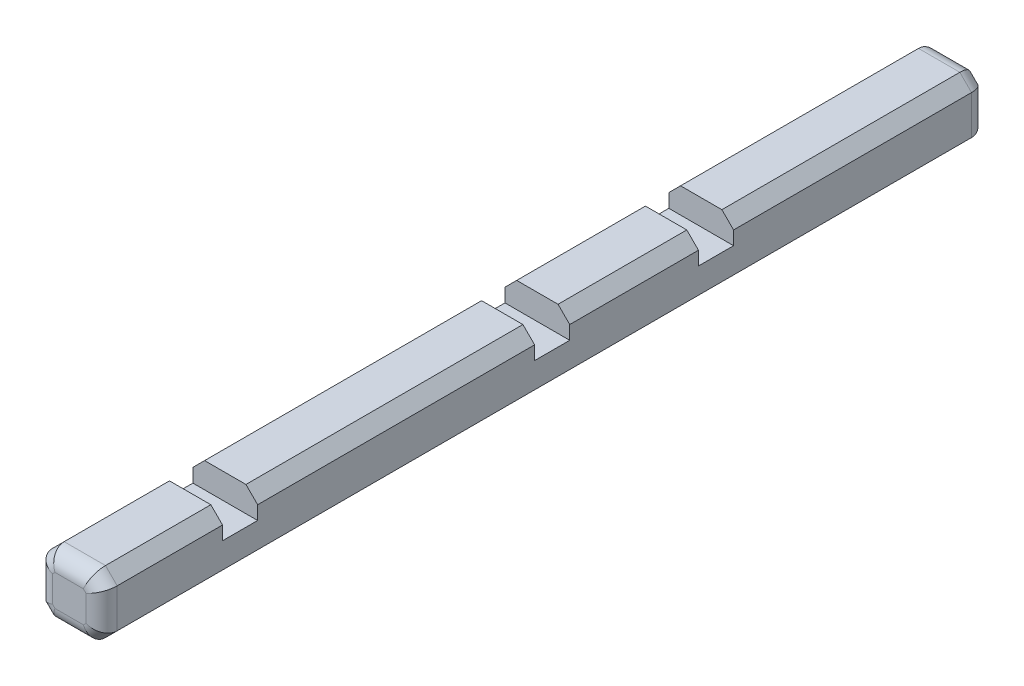
SolidWorks part; units mm, degrees
ref_plane "Front Plane" through (0, 0, 0) normal (0, 0, 1) x (1, 0, 0)
ref_plane "Top Plane" through (0, 0, 0) normal (0, 1, 0) x (1, 0, 0)
ref_plane "Right Plane" through (0, 0, 0) normal (1, 0, 0) x (0, 0, -1)
sketch "Sketch1" plane through (0, 0, 0) normal (0, 0, 1) x (1, 0, 0)
  line L1 (4.15, -4) -> (-4.15, -4)
  line L2 (4.15, -4) -> (4.15, 4)
  line L3 (4.15, 4) -> (-4.15, 4)
  line L4 (-4.15, -4) -> (-4.15, 4)
  point P0 (0, 4)
  point P1 (-4.15, 0)
  dimension "D1" = 8.3
  dimension "D2" = 8
extrude "Boss-Extrude1" add sketch "Sketch1" along normal blind 113.5
chamfer "Chamfer2" distance 1.5 angle 45 4 edges at (4.15, -4, 56.75) (-4.15, -4, 56.75) (4.15, 4, 56.75) (-4.15, 4, 56.75)
sketch "Sketch2" plane through (0, 0, 0) normal (0, 1, 0) x (1, 0, 0)
  line L0 (2.65, -113.5) -> (-2.65, -113.5) construction
  point P0 (0, -58)
  point P3 (0, -113.5)
  point P4 (0, -37)
  point P5 (0, -98)
  dimension "D1" = 55.5
  dimension "D2" = 15.5
  dimension "D3" = 21
ref_plane "Plane1" through (0, 0, 58) normal (0, 0, -1) x (-1, 0, 0)
sketch "Sketch3" plane through (0, 0, 58) normal (0, 0, -1) x (-1, 0, 0)
  line L0 (-4.15, -2.5) -> (-4.15, 2.5) construction
  line L1 (-4.15, 0.75) -> (4.15, 0.75)
  line L2 (-4.15, 0.75) -> (-4.15, 4)
  line L3 (-4.15, 4) -> (4.15, 4)
  line L4 (4.15, 0.75) -> (4.15, 4)
  line L5 (4.15, 2.5) -> (4.15, -2.5) construction
  line L6 (-2.65, 4) -> (2.65, 4) construction
  dimension "D1" = 3.25
extrude "Cut-Extrude1" cut sketch "Sketch3" along normal blind 4.5
ref_plane "Plane2" through (0, 0, 98) normal (0, 0, -1) x (-1, 0, 0)
sketch "Sketch4" plane through (0, 0, 98) normal (0, 0, -1) x (-1, 0, 0)
  line L0 (-4.15, -2.5) -> (-4.15, 2.5) construction
  line L1 (-4.15, 0.75) -> (4.15, 0.75)
  line L2 (-4.15, 0.75) -> (-4.15, 4)
  line L3 (-4.15, 4) -> (4.15, 4)
  line L4 (4.15, 0.75) -> (4.15, 4)
  line L5 (4.15, 2.5) -> (4.15, -2.5) construction
  line L6 (-2.65, 4) -> (2.65, 4) construction
  dimension "D1" = 3.25
extrude "Cut-Extrude2" cut sketch "Sketch4" along normal blind 4.5
fillet "Fillet1" radius 2 16 edges at (0, 4, 0) (-4.15, 0, 0) (0, -4, 0) (4.15, 0, 0) (-4.15, 0, 113.5) (0, 4, 113.5) (4.15, 0, 113.5) (0, -4, 113.5) (3.4, 3.25, 0) (-3.4, 3.25, 0) (-3.4, -3.25, 0) (3.4, -3.25, 0) (-3.4, -3.25, 113.5) (-3.4, 3.25, 113.5) (3.4, 3.25, 113.5) (3.4, -3.25, 113.5)
ref_plane "Plane3" through (0, 0, 37) normal (0, 0, -1) x (-1, 0, 0)
sketch "Sketch6" plane through (0, 0, 37) normal (0, 0, -1) x (-1, 0, 0)
  line L1 (-4.15, 4) -> (4.15, 4)
  line L2 (-4.15, 4) -> (-4.15, 0.75)
  line L3 (-4.15, 0.75) -> (4.15, 0.75)
  line L4 (4.15, 4) -> (4.15, 0.75)
extrude "Cut-Extrude3" cut sketch "Sketch6" along normal blind 4.5
ref_plane "Plane4" through (0, 0, 58) normal (0, 0, 1) x (1, 0, 0)
sketch "Sketch8" plane through (0, 0, 58) normal (0, 0, 1) x (1, 0, 0)
  circle A0 centre (0, 0) radius 5.214
ref_plane "Plane5" through (0, 0, 93.5) normal (0, 0, 1) x (1, 0, 0)
sketch "Sketch9" plane through (0, 0, 93.5) normal (0, 0, 1) x (1, 0, 0)
  line L0 (0, 4) -> (0, -4) construction
  line L1 (-2.65, 4) -> (2.65, 4) construction
  line L2 (2.65, -4) -> (-2.65, -4) construction
  line L3 (-4.15, 0) -> (4.15, 0) construction
  line L4 (-4.15, -2.5) -> (-4.15, 2.5) construction
  line L5 (4.15, 2.5) -> (4.15, -2.5) construction
ref_plane "Plane6" through (0, 0, 53.5) normal (0, 0, 1) x (1, 0, 0)
sketch "Sketch10" plane through (0, 0, 53.5) normal (0, 0, 1) x (1, 0, 0)
  line L0 (0, 4) -> (0, -4) construction
  line L1 (-4.15, 0) -> (4.15, 0) construction
  line L2 (-4.15, -2.5) -> (-4.15, 2.5) construction
sketch "Sketch11" plane through (0, 0, 37) normal (0, 0, -1) x (-1, 0, 0)
  line L0 (0, 4) -> (0, -4) construction
  line L1 (-4.15, 0) -> (4.15, 0) construction
equation "\"thiccness\"=4.5"
equation "\"D1@Cut-Extrude1\"=\"thiccness\""
equation "\"cut\"=3.25"
equation "\"D1@Sketch4\"=\"cut\""
equation "\"D1@Cut-Extrude2\"=\"thiccness\""
equation "\"D1@Sketch3\"=\"cut\""
